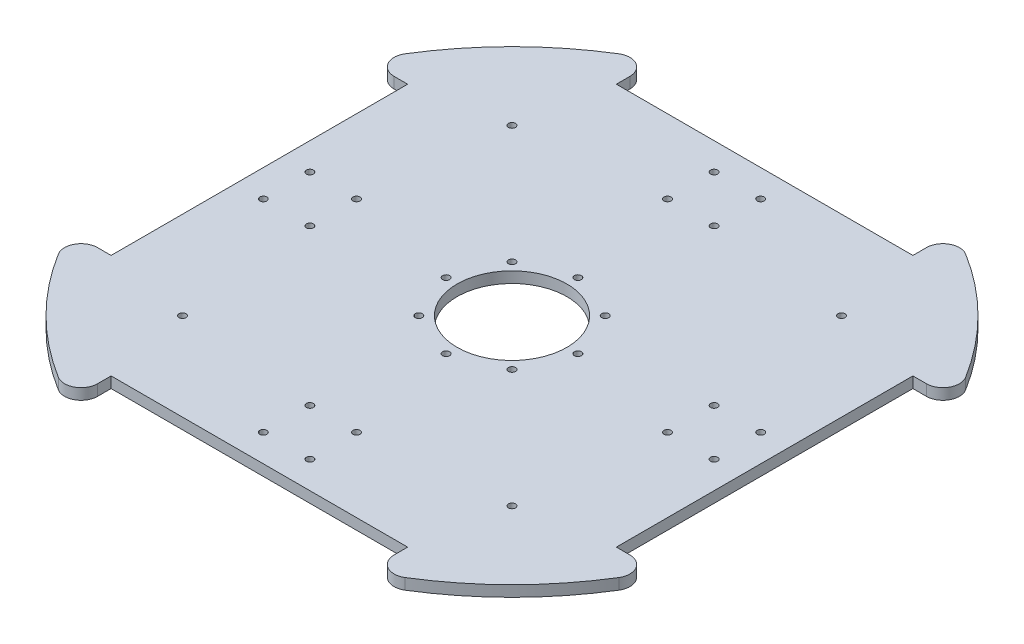
SolidWorks part; units mm, degrees
ref_plane "Front Plane" through (0, 0, 0) normal (0, 0, 1) x (1, 0, 0)
ref_plane "Top Plane" through (0, 0, 0) normal (0, 1, 0) x (1, 0, 0)
ref_plane "Right Plane" through (0, 0, 0) normal (1, 0, 0) x (0, 0, -1)
sketch "Sketch1" plane through (0, 0, 0) normal (0, 1, 0) x (1, 0, 0)
  line L0 (160, 67.5) -> (115, 67.5)
  line L5 (-67.5, 160) -> (67.5, 160)
  line L6 (-67.5, 160) -> (-67.5, 115)
  line L7 (-67.5, 115) -> (67.5, 115)
  line L8 (67.5, 160) -> (67.5, 115)
  line L9 (160, 67.5) -> (160, -67.5)
  line L10 (160, -67.5) -> (115, -67.5)
  line L11 (115, 67.5) -> (115, -67.5)
  line L12 (67.5, -160) -> (67.5, -115)
  line L13 (67.5, -160) -> (-67.5, -160)
  line L14 (-67.5, -160) -> (-67.5, -115)
  line L15 (67.5, -115) -> (-67.5, -115)
  line L16 (-160, -67.5) -> (-115, -67.5)
  line L17 (-160, -67.5) -> (-160, 67.5)
  line L18 (-160, 67.5) -> (-115, 67.5)
  line L19 (-115, -67.5) -> (-115, 67.5)
  line L20 (0, 150) -> (0, 115) construction
  line L21 (0, 160) -> (0, 150) construction
  circle A0 centre (0, 0) radius 150
  point P7 (0, 115)
  point P23 (0, 0)
  dimension "D1" = 300
  dimension "D4" = 35
  dimension "D2" = 135
  dimension "D5" = 10
  dimension "D3" = 4
extrude "Boss-Extrude1" add sketch "Sketch1" along normal blind 5 contours L12 A0 L10 L11 L0 L8 L7 L6 L18 L19 L16 L14 L15 region at (0, 0, 0)
fillet "Fillet1" radius 7.5 8 edges at (-133.9543, 2.5, 67.5) (-133.9543, 2.5, -67.5) (-67.5, 2.5, -133.9543) (67.5, 2.5, -133.9543) (133.9543, 2.5, -67.5) (133.9543, 2.5, 67.5) (67.5, 2.5, 133.9543) (-67.5, 2.5, 133.9543)
sketch "Sketch3" plane through (0, 5, 0) normal (0, 1, 0) x (1, 0, 0)
  line L0 (0, -115) -> (0, -92) construction
  line L1 (67.5, -115) -> (-67.5, -115) construction
  line L2 (-10.6066, -102.6066) -> (10.6066, -102.6066) construction
  line L3 (-115, 0) -> (-92, 0) construction
  line L4 (-102.6066, 10.6066) -> (-102.6066, -10.6066) construction
  line L5 (0, 115) -> (0, 92) construction
  line L6 (10.6066, 102.6066) -> (-10.6066, 102.6066) construction
  line L7 (115, 0) -> (92, 0) construction
  line L8 (102.6066, -10.6066) -> (102.6066, 10.6066) construction
  line L9 (-115, -67.5) -> (-115, 67.5) construction
  circle A0 centre (-10.6066, -102.6066) radius 1.6
  circle A1 centre (-10.6066, -81.3934) radius 1.6
  circle A2 centre (10.6066, -81.3934) radius 1.6
  circle A3 centre (10.6066, -102.6066) radius 1.6
  circle A4 centre (-81.3934, 10.6066) radius 1.6
  circle A5 centre (-81.3934, -10.6066) radius 1.6
  circle A6 centre (-102.6066, -10.6066) radius 1.6
  circle A7 centre (-102.6066, 10.6066) radius 1.6
  circle A8 centre (10.6066, 81.3934) radius 1.6
  circle A9 centre (-10.6066, 81.3934) radius 1.6
  circle A10 centre (-10.6066, 102.6066) radius 1.6
  circle A11 centre (10.6066, 102.6066) radius 1.6
  circle A12 centre (81.3934, -10.6066) radius 1.6
  circle A13 centre (81.3934, 10.6066) radius 1.6
  circle A14 centre (102.6066, 10.6066) radius 1.6
  circle A15 centre (102.6066, -10.6066) radius 1.6
  point P7 (0, -102.6066)
  point P16 (0, -92)
  point P48 (0, 0)
  dimension "D1" = 3.2
  dimension "D2" = 15
  dimension "D3" = 23
  dimension "D4" = 4
  dimension "D5" = 4
extrude "Cut-Extrude2" cut sketch "Sketch3" against normal through all both and the other way through all
sketch "Sketch4" plane through (0, 5, 0) normal (0, 1, 0) x (1, 0, 0)
  circle A0 centre (0, 0) radius 25
  circle A1 centre (0, 30) radius 1.6
  circle A2 centre (21.2132, 21.2132) radius 1.6
  circle A3 centre (30, 0) radius 1.6
  circle A4 centre (21.2132, -21.2132) radius 1.6
  circle A5 centre (0, -30) radius 1.6
  circle A6 centre (-21.2132, -21.2132) radius 1.6
  circle A7 centre (-30, 0) radius 1.6
  circle A8 centre (-21.2132, 21.2132) radius 1.6
  point P22 (0, 0)
  dimension "D1" = 50
  dimension "D2" = 3.2
  dimension "D3" = 30
  dimension "D4" = 8
extrude "Cut-Extrude3" cut sketch "Sketch4" against normal through all both and the other way through all
sketch "Sketch5" plane through (0, 5, 0) normal (0, 1, 0) x (1, 0, 0)
  line L0 (75, -75) -> (106.066, -106.066) construction
  line L1 (-75, -75) -> (-106.066, -106.066) construction
  line L2 (-115, 0) -> (115, 0) construction
  line L3 (-115, -67.5) -> (-115, 67.5) construction
  line L4 (115, 67.5) -> (115, -67.5) construction
  circle A0 centre (75, -75) radius 1.6
  circle A1 centre (-75, -75) radius 1.6
  arc A2 (78.9474, -127.5434) -> (127.5434, -78.9474) centre (0, 0) ccw construction
  arc A3 (-127.5434, -78.9474) -> (-78.9474, -127.5434) centre (0, 0) ccw construction
  circle A9 centre (75, 75) radius 1.6
  circle A10 centre (-75, 75) radius 1.6
  dimension "D1" = 3.2
  dimension "D2" = 150
extrude "Cut-Extrude4" cut sketch "Sketch5" against normal through all both and the other way through all
